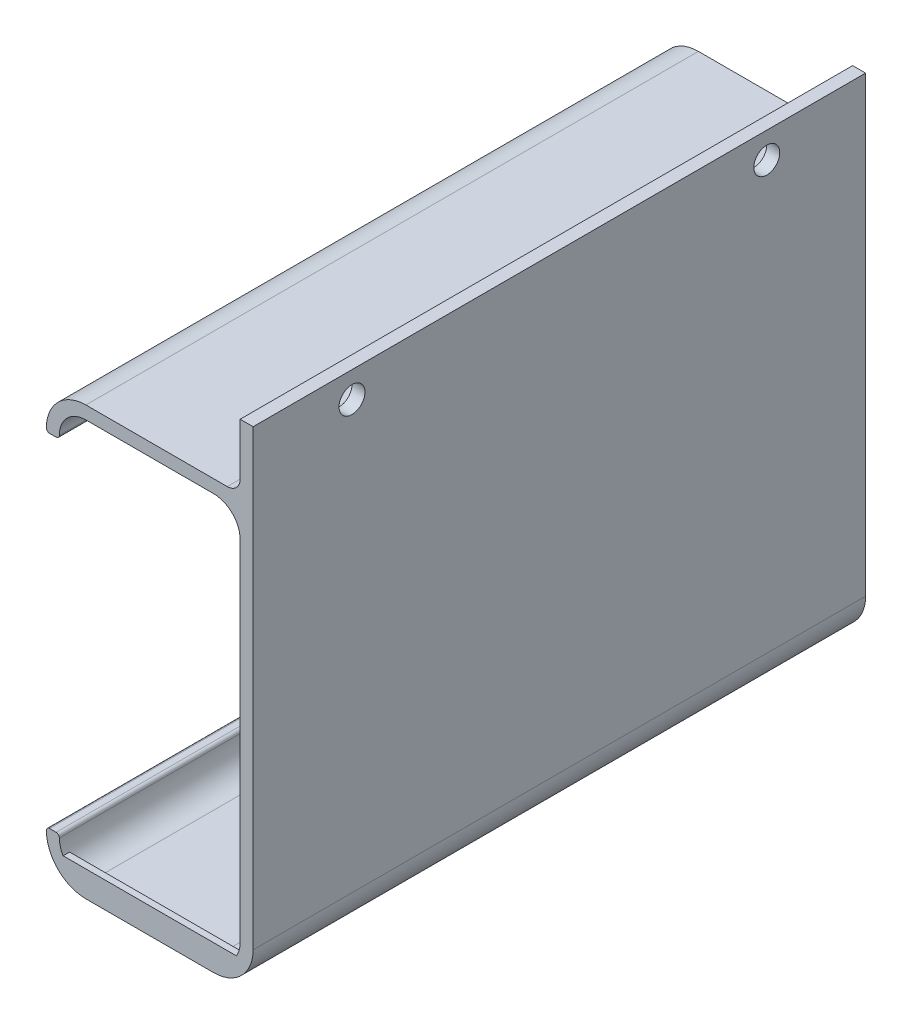
SolidWorks part; units mm, degrees
ref_plane "Front Plane" through (0, 0, 0) normal (1, 0, 0) x (0, 1, 0)
ref_plane "Top Plane" through (0, 0, 0) normal (0, 0, 1) x (0, 1, 0)
ref_plane "Right Plane" through (0, 0, 0) normal (0, 1, 0) x (-1, 0, 0)
sketch "Sketch1" plane through (0, 0, 0) normal (0, 0, 1) x (0, 1, 0)
  line L0 (-26.9, 13.95) -> (-26.4, 13.95)
  line L1 (-26.9, -13.85) -> (26.9, -13.85) construction
  line L2 (-30.9, -9.85) -> (-30.9, 9.85) construction
  line L3 (-26.9, 13.85) -> (26.9, 13.85) construction
  line L4 (30.9, -9.85) -> (30.9, 9.85) construction
  line L5 (-30.9, -13.85) -> (30.9, 13.85) construction
  line L6 (-30.9, 13.85) -> (30.9, -13.85) construction
  line L7 (31, -9.85) -> (31, 9.85)
  line L8 (-26.9, -13.95) -> (26.9, -13.95)
  line L9 (-31, -9.85) -> (-31, 9.85)
  line L10 (-26.9, 15.95) -> (-26.4, 15.95)
  line L11 (33, -9.85) -> (33, 9.85)
  line L12 (-26.9, -15.95) -> (26.9, -15.95)
  line L13 (-33, -9.85) -> (-33, 9.85)
  line L14 (-26.4, 15.95) -> (-26.4, 13.95)
  line L15 (0, 0) -> (0, 42.4171) construction
  line L16 (26.4, 15.95) -> (26.4, 13.95)
  line L17 (26.4, 15.95) -> (26.9, 15.95)
  line L18 (-26.9, 15.95) -> (26.9, 15.95) construction
  line L19 (26.4, 13.95) -> (26.9, 13.95)
  line L20 (-26.9, 13.95) -> (26.9, 13.95) construction
  line L21 (26.9, -15.95) -> (43, -15.95)
  line L22 (35, -13.95) -> (43, -13.95)
  line L23 (43, -13.95) -> (43, -15.95)
  line L24 (33, -9.85) -> (33, -11.95)
  arc A0 (-30.9, 9.85) -> (-26.9, 13.85) centre (-26.9, 9.85) cw construction
  arc A1 (-26.9, -13.85) -> (-30.9, -9.85) centre (-26.9, -9.85) cw construction
  arc A2 (26.9, -13.85) -> (30.9, -9.85) centre (26.9, -9.85) ccw construction
  arc A3 (26.9, 13.85) -> (30.9, 9.85) centre (26.9, 9.85) cw construction
  arc A4 (26.9, 13.95) -> (31, 9.85) centre (26.9, 9.85) cw
  arc A5 (26.9, -13.95) -> (31, -9.85) centre (26.9, -9.85) ccw
  arc A6 (-26.9, -13.95) -> (-31, -9.85) centre (-26.9, -9.85) cw
  arc A7 (-31, 9.85) -> (-26.9, 13.95) centre (-26.9, 9.85) cw
  arc A8 (26.9, 15.95) -> (33, 9.85) centre (26.9, 9.85) cw
  arc A9 (26.9, -15.95) -> (33, -9.85) centre (26.9, -9.85) ccw construction
  arc A10 (-26.9, -15.95) -> (-33, -9.85) centre (-26.9, -9.85) cw
  arc A11 (-33, 9.85) -> (-26.9, 15.95) centre (-26.9, 9.85) cw
  arc A12 (33, -11.95) -> (35, -13.95) centre (35, -11.95) ccw
  point P0 (0, 0)
  dimension "D3" = 4
  dimension "D7" = 2
  dimension "D1" = 61.8
  dimension "D2" = 27.7
  dimension "D6" = 0.5
  dimension "D8" = 8
  dimension "D4" = 0.1
  dimension "D5" = 2
extrude "Boss-Extrude1" add sketch "Sketch1" along normal mid plane 92.5
fillet "Fillet1" radius 0.5 4 edges at (-15.95, 26.4, 0) (-13.95, 26.4, 0) (-13.95, -26.4, 0) (-15.95, -26.4, 0)
sketch "Sketch2" plane through (0, 0, 46.25) normal (0, 0, 1) x (1, 0, 0)
  line L1 (-13.3714, -29) -> (13.3714, -29)
  line L8 (-15.45, 26.4) -> (-14.45, 26.4)
  line L9 (-9.85, 31) -> (9.85, 31)
  line L10 (13.95, 26.9) -> (13.95, -26.9)
  line L11 (9.85, -31) -> (-9.85, -31)
  line L12 (-14.45, -26.4) -> (-15.45, -26.4)
  line L13 (-9.85, -33) -> (9.85, -33)
  line L14 (15.95, -26.9) -> (15.95, 43)
  line L15 (11.95, 33) -> (-9.85, 33)
  line L16 (-15.45, 26.4) -> (-14.45, 26.4)
  line L17 (-9.85, 31) -> (9.85, 31)
  line L18 (13.95, 26.9) -> (13.95, -26.9)
  line L19 (9.85, -31) -> (-9.85, -31) construction
  line L20 (-14.45, -26.4) -> (-15.45, -26.4)
  line L21 (-9.85, -33) -> (9.85, -33)
  line L22 (15.95, -26.9) -> (15.95, 43)
  line L23 (11.95, 33) -> (-9.85, 33)
  line L27 (15.95, 43) -> (13.95, 43)
  line L28 (15.95, 43) -> (13.95, 43)
  line L29 (13.95, 43) -> (13.95, 35)
  line L30 (13.95, 43) -> (13.95, 35)
  arc A12 (-9.85, 33) -> (-15.95, 26.9) centre (-9.85, 26.9) ccw
  arc A13 (-15.95, 26.9) -> (-15.45, 26.4) centre (-15.45, 26.9) ccw
  arc A14 (-14.45, 26.4) -> (-13.95, 26.9) centre (-14.45, 26.9) ccw
  arc A15 (-9.85, 31) -> (-13.95, 26.9) centre (-9.85, 26.9) ccw
  arc A16 (13.95, 26.9) -> (9.85, 31) centre (9.85, 26.9) ccw
  arc A17 (9.85, -31) -> (13.95, -26.9) centre (9.85, -26.9) ccw
  arc A18 (-13.95, -26.9) -> (-9.85, -31) centre (-9.85, -26.9) ccw
  arc A19 (-13.95, -26.9) -> (-14.45, -26.4) centre (-14.45, -26.9) ccw
  arc A20 (-15.45, -26.4) -> (-15.95, -26.9) centre (-15.45, -26.9) ccw
  arc A21 (-15.95, -26.9) -> (-9.85, -33) centre (-9.85, -26.9) ccw
  arc A22 (9.85, -33) -> (15.95, -26.9) centre (9.85, -26.9) ccw
  arc A23 (11.95, 33) -> (13.95, 35) centre (11.95, 35) ccw
  arc A24 (-9.85, 33) -> (-15.95, 26.9) centre (-9.85, 26.9) ccw
  arc A25 (-15.95, 26.9) -> (-15.45, 26.4) centre (-15.45, 26.9) ccw
  arc A26 (-14.45, 26.4) -> (-13.95, 26.9) centre (-14.45, 26.9) ccw
  arc A27 (-9.85, 31) -> (-13.95, 26.9) centre (-9.85, 26.9) ccw
  arc A28 (13.95, 26.9) -> (9.85, 31) centre (9.85, 26.9) ccw
  arc A29 (13.3714, -29) -> (13.95, -26.9) centre (9.85, -26.9) ccw
  arc A30 (-13.95, -26.9) -> (-13.3714, -29) centre (-9.85, -26.9) ccw
  arc A31 (-13.95, -26.9) -> (-14.45, -26.4) centre (-14.45, -26.9) ccw
  arc A32 (-15.45, -26.4) -> (-15.95, -26.9) centre (-15.45, -26.9) ccw
  arc A33 (-15.95, -26.9) -> (-9.85, -33) centre (-9.85, -26.9) ccw
  arc A34 (9.85, -33) -> (15.95, -26.9) centre (9.85, -26.9) ccw
  arc A36 (11.95, 33) -> (13.95, 35) centre (11.95, 35) ccw
  dimension "D2" = 2
  dimension "D1" = 0
extrude "Boss-Extrude2" add sketch "Sketch2" along normal blind 1
mirror "Mirror1" about plane through (0, 0, 0) normal (0, 0, 1) of "Boss-Extrude2"
sketch "Sketch3" plane through (13.95, 0, 0) normal (-1, 0, 0) x (0, -1, 0)
  line L0 (-39, 47.25) -> (-39, -47.25) construction
  line L1 (-43, 47.25) -> (-35, 47.25) construction
  line L2 (-43, -47.25) -> (-35, -47.25) construction
  line L3 (-43, 0) -> (-35, 0) construction
  line L4 (-43, 47.25) -> (-43, -47.25) construction
  line L5 (-35, 47.25) -> (-35, -47.25) construction
  circle A0 centre (-39, 32) radius 4 construction
  circle A1 centre (-39, 32) radius 2
  circle A2 centre (-39, -32) radius 2
  dimension "D1" = 8
  dimension "D2" = 4
  dimension "D3" = 32
extrude "Cut-Extrude1" cut sketch "Sketch3" against normal blind 21
